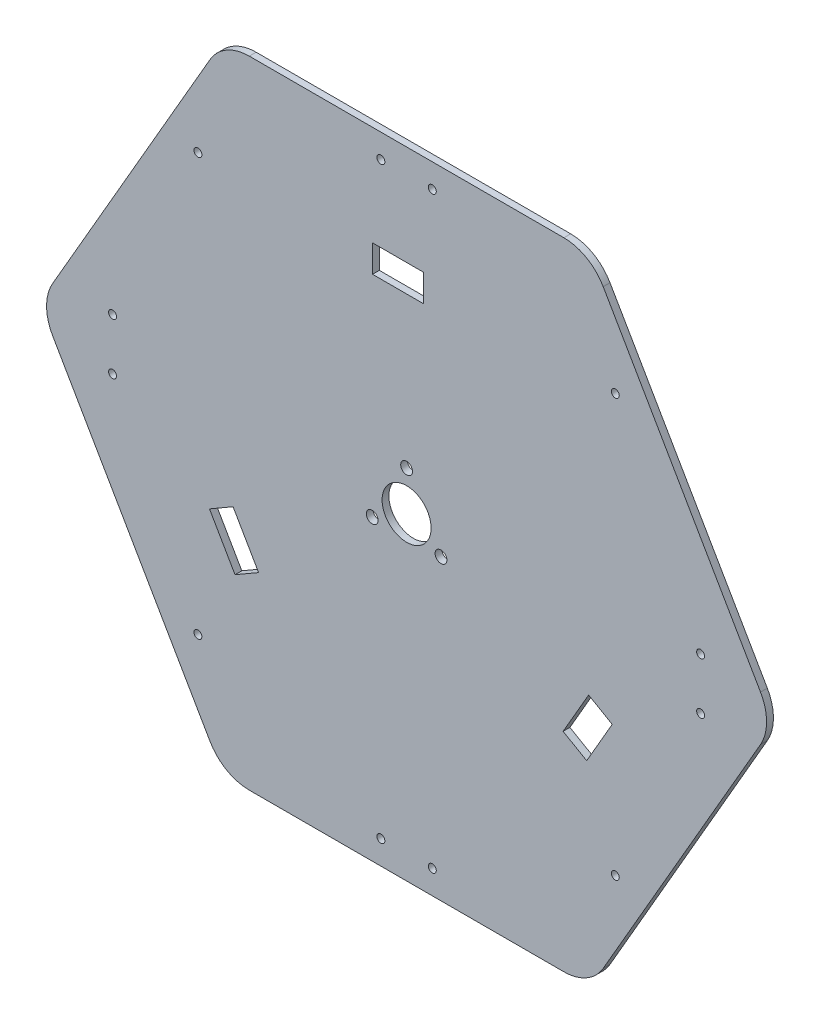
SolidWorks part; units mm, degrees
ref_plane "Alzado" through (0, 0, 0) normal (0, 0, 1) x (1, 0, 0)
ref_plane "Planta" through (0, 0, 0) normal (0, 1, 0) x (1, 0, 0)
ref_plane "Vista lateral" through (0, 0, 0) normal (1, 0, 0) x (0, 0, -1)
sketch "Croquis1" plane through (0, 0, 0) normal (0, 0, 1) x (1, 0, 0)
  line L0 (7.5, 95.9218) -> (-15, 83.9218) construction
  line L1 (-15, 95.9218) -> (7.5, 95.9218)
  line L2 (-15, 95.9218) -> (-15, 83.9218)
  line L3 (-15, 83.9218) -> (7.5, 83.9218)
  line L4 (7.5, 95.9218) -> (7.5, 83.9218)
  line L5 (-15, 95.9218) -> (7.5, 83.9218) construction
  line L6 (90.5708, -34.9705) -> (80.1784, -28.9705)
  line L7 (90.5708, -34.9705) -> (79.3208, -54.4561)
  line L8 (79.3208, -54.4561) -> (68.9284, -48.4561)
  line L9 (80.1784, -28.9705) -> (68.9284, -48.4561)
  line L10 (-75.5708, -60.9513) -> (-65.1784, -54.9513)
  line L11 (-75.5708, -60.9513) -> (-86.8208, -41.4657)
  line L12 (-86.8208, -41.4657) -> (-76.4284, -35.4657)
  line L13 (-65.1784, -54.9513) -> (-76.4284, -35.4657)
  line L14 (0, -0.7536) -> (0, 0) construction
  line L15 (0, 0) -> (0, 17.5) construction
  line L17 (-80.829, -140) -> (80.829, -140)
  line L18 (80.829, -140) -> (161.6581, 0)
  line L19 (161.6581, 0) -> (80.829, 140)
  line L20 (80.829, 140) -> (-80.829, 140)
  line L21 (-80.829, 140) -> (-161.6581, 0)
  line L22 (-161.6581, 0) -> (-80.829, -140)
  circle A0 centre (0, 0) radius 150
  circle A1 centre (0, 0) radius 10.8
  circle A2 centre (0, 0) radius 90 construction
  circle A3 centre (-3.75, 89.9218) radius 40 construction
  circle A4 centre (79.7496, -41.7133) radius 40 construction
  circle A5 centre (-75.9996, -48.2085) radius 40 construction
  circle A6 centre (0, 0) radius 17.5 construction
  circle A7 centre (0, 17.5) radius 2.6
  circle A8 centre (0, 0) radius 140 construction
  circle A9 centre (15.1554, -8.75) radius 2.6
  circle A10 centre (-15.1554, -8.75) radius 2.6
  point P11 (-3.75, 89.9218)
  point P18 (0, 0)
  point P28 (0, 0)
  point P39 (0, 0)
  point P46 (0, 140)
  dimension "D1" = 300
  dimension "D2" = 21.6
  dimension "D3" = 180
  dimension "D4" = 80
  dimension "D9" = 5.2
  dimension "D10" = 3
  dimension "D11" = 50
  dimension "D5" = 12
  dimension "D6" = 22.5
  dimension "D12" = 3.75
  dimension "D7" = 3
  dimension "D8" = 3
extrude "Saliente-Extruir1" add sketch "Croquis1" along normal blind 3 contours L19 A0 L20 L21 L22 L17 L18 A10 A9 A7 A1 L1 L4 L3 L2 L9 L6 L7 L8 L13 L10 L11 L12 | A0 L20 L21 | A0 L19 L20 | A0 L18 L19 | A0 L17 L18 | A0 L22 L17 | A0 L21 L22 region at (-76.7492, -132.9335, 0) region at (-72.9482, -126.3499, 0) region at (76.7492, -132.9335, 0) region at (-153.4984, 0, 0) region at (153.4984, 0, 0) region at (-76.7492, 132.9335, 0) region at (76.7492, 132.9335, 0)
fillet "Redondeo1" radius 20 6 edges at (80.829, 140, 1.5) (-80.829, 140, 1.5) (-161.6581, 0, 1.5) (-80.829, -140, 1.5) (80.829, -140, 1.5) (161.6581, 0, 1.5)
sketch "Croquis2" plane through (0, 0, 0) normal (0, 0, -1) x (-1, 0, 0)
  circle A0 centre (0, 0) radius 102.5 construction
  circle A1 centre (0, 0) radius 140 construction
  dimension "D1" = 280
  dimension "D2" = 205
sketch "Croquis3" plane through (0, 0, 0) normal (0, 0, -1) x (1, 0, 0)
  circle A0 centre (129.5053, 11.3302) radius 1.75
  circle A1 centre (91.9239, 91.9239) radius 1.75
  circle A2 centre (11.3302, 129.5053) radius 1.75
extrude "Cortar-Extruir1" cut sketch "Croquis3" against normal through all
pattern_circular "MatrizC1" count 4 over 360 about axis through (0, 0, 0) along (0, 0, 1) of "Cortar-Extruir1"
